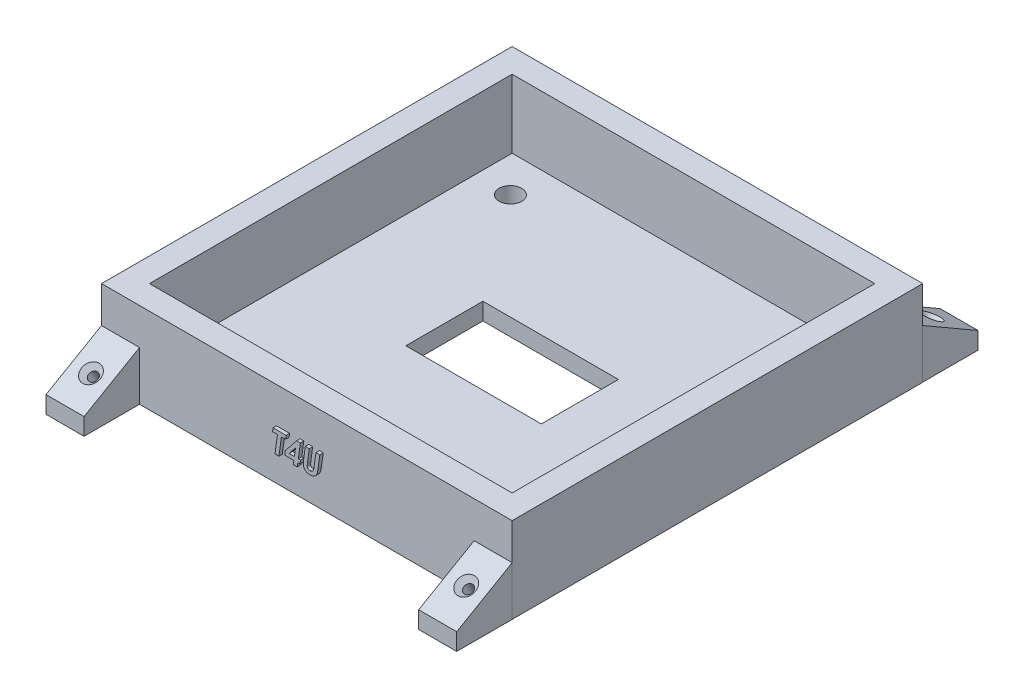
SolidWorks part; units mm, degrees
ref_plane "Front" through (0, 0, 0) normal (0, 0, 1) x (1, 0, 0)
ref_plane "Top" through (0, 0, 0) normal (0, 1, 0) x (1, 0, 0)
ref_plane "Right" through (0, 0, 0) normal (1, 0, 0) x (0, 0, -1)
sketch "Sketch1" plane through (0, 0, 0) normal (0, 1, 0) x (1, 0, 0)
  line L0 (-47.9687, 57.8349) -> (58.0313, 57.8349)
  line L2 (-54.9687, 64.8349) -> (-54.9687, -55.1651)
  line L4 (65.0313, 64.8349) -> (65.0313, -55.1651)
  line L5 (-54.9687, 64.8349) -> (65.0313, -55.1651) construction
  line L6 (-54.9687, -55.1651) -> (65.0313, 64.8349) construction
  line L7 (58.0313, 57.8349) -> (58.0313, -48.1651)
  line L8 (-47.9687, -48.1651) -> (58.0313, -48.1651)
  line L9 (-47.9687, 57.8349) -> (-47.9687, -48.1651)
  line L10 (5.0313, 122.0539) -> (5.0313, -165.2427) construction
  line L16 (-43.869, 64.8349) -> (-43.869, 81.0517)
  line L17 (-54.9687, -72.3819) -> (-54.9687, -55.1651) construction
  line L18 (-111.8398, 4.8349) -> (163.782, 4.8349) construction
  line L19 (-54.9687, -55.1651) -> (-42.869, -72.3819) construction
  line L20 (65.0313, -52.0306) -> (56.1043, -48.1651) construction
  line L24 (53.9479, 81.0517) -> (65.0313, 64.8349) construction
  line L25 (53.9316, 64.8349) -> (64.9733, 81.0517) construction
  line L29 (65.0313, -55.1651) -> (53.1585, -72.537) construction
  line L30 (65.0313, -72.3819) -> (65.0313, -55.1651) construction
  line L34 (53.9316, 64.8349) -> (53.9316, 81.0517)
  line L35 (-14.7657, 16.0987) -> (24.8283, 16.0987)
  line L36 (-14.7657, 16.0987) -> (-14.7657, -6.4289)
  line L37 (-14.7657, -6.4289) -> (24.8283, -6.4289)
  line L38 (24.8283, 16.0987) -> (24.8283, -6.4289)
  line L39 (-14.7657, 16.0987) -> (24.8283, -6.4289) construction
  line L40 (-14.7657, -6.4289) -> (24.8283, 16.0987) construction
  line L41 (64.9733, 81.0517) -> (53.9316, 81.0517)
  line L42 (64.9733, 64.8349) -> (64.9733, 81.0517)
  line L47 (-54.99, -55.1651) -> (-54.99, -71.3819)
  line L48 (-54.99, -71.3819) -> (-43.869, -71.3819)
  line L49 (-43.869, -55.1651) -> (-43.869, -71.3819)
  line L50 (53.9316, -55.1651) -> (53.9316, -71.3819)
  line L51 (65.0476, -71.3819) -> (53.9316, -71.3819)
  line L52 (65.0476, -55.1651) -> (65.0476, -71.3819)
  line L53 (-54.9107, 81.0517) -> (-43.869, 81.0517)
  line L56 (-54.9107, 64.8349) -> (-54.9107, 81.0517)
  line L57 (53.9316, 64.8349) -> (64.9733, 64.8349)
  line L58 (59.4524, 81.0517) -> (59.4524, 64.8349) construction
  line L59 (-54.9687, 64.8349) -> (65.0313, 64.8349) construction
  line L60 (-54.9687, 64.8349) -> (65.0313, 64.8349)
  line L61 (-54.9687, -55.1651) -> (65.0313, -55.1651)
  line L63 (-54.9687, -55.1651) -> (65.0313, -55.1651) construction
  line L64 (53.9316, 72.9433) -> (64.9733, 72.9433) construction
  line L65 (-54.99, -55.1651) -> (-43.869, -55.1651)
  line L66 (-43.869, 64.8349) -> (-54.9107, 64.8349)
  line L69 (53.9316, -55.1651) -> (65.0476, -55.1651)
  line L70 (53.9316, -63.2735) -> (65.0476, -63.2735) construction
  line L71 (59.4896, -71.3819) -> (59.4896, -55.1651) construction
  line L72 (-54.99, -63.2735) -> (-43.869, -63.2735) construction
  line L73 (-49.4295, -71.3819) -> (-49.4295, -55.1651) construction
  line L74 (-54.9107, 72.9433) -> (-43.869, 72.9433) construction
  line L75 (-49.3899, 81.0517) -> (-49.3899, 64.8349) construction
  line L76 (-43.869, 81.0517) -> (-54.9107, 64.8349) construction
  line L77 (-54.9107, 81.0517) -> (-43.869, 64.8349) construction
  point P0 (5.0313, 4.8349)
  point P41 (5.0313, 4.8349)
  dimension "D2" = 7
extrude "Boss-Extrude1" add sketch "Sketch1" along normal blind 5 contours L0 L9 L8 L7 L35 L38 L37 L36 region at (5.0313, 0, -56.3358)
extrude "Boss-Extrude2" add sketch "Sketch1<4>" along normal blind 25 contours L4 L2 L9 L0 L7 L8 region at (-54.9397, 0, -63.1378)
sketch "Sketch1<4>" plane through (0, 0, 0) normal (0, 1, 0) x (1, 0, 0) same geometry as "Sketch1"
extrude "Boss-Extrude4" add sketch "Sketch1<6>" along normal blind 5
sketch "Sketch1<6>" plane through (0, 0, 0) normal (0, 1, 0) x (1, 0, 0) same geometry as "Sketch1"
extrude "Boss-Extrude5" add sketch "Sketch1<8>" along normal blind 5 contours L42 L41 L34 region at (59.4524, 0, -72.9433)
sketch "Sketch1<8>" plane through (0, 0, 0) normal (0, 1, 0) x (1, 0, 0) same geometry as "Sketch1"
extrude "Boss-Extrude7" add sketch "Sketch1<10>" along normal blind 5 contours L69 L50 L51 L52 | L65 L47 L48 L49 region at (-49.4295, 0, 63.2735) region at (59.4896, 0, 63.2735)
sketch "Sketch1<10>" plane through (0, 0, 0) normal (0, 1, 0) x (1, 0, 0) same geometry as "Sketch1"
draft "Draft1" type of draft neutral plane draft angle 1 faces to draft 1 face at (60.598, 5, 61.6518) neutral plane through (0, 5, 71.3819) neutral plane normal (0, 0, 1) parameters "D1"=1
draft "Draft2" type of draft neutral plane draft angle 45 faces to draft 1 face at (60.598, 5.1698, 61.6518) neutral plane through (0, 5, 71.3819) neutral plane normal (0, 0, 1) parameters "D1"=45
draft "Draft3" type of draft neutral plane draft angle 30 faces to draft 1 face at (60.598, 14.7301, 61.6518) neutral plane through (0, 5, 71.3819) neutral plane normal (0, 0, 1) parameters "D1"=30
draft "Draft4" type of draft neutral plane draft angle 30 faces to draft 1 face at (-50.5374, 5, 61.6518) neutral plane through (0, 5, 71.3819) neutral plane normal (0, 0, 1) parameters "D1"=30
draft "Draft6" type of draft neutral plane draft angle 30 faces to draft 1 face at (-49.3899, 5, -72.9433) neutral plane through (0, 5, -81.0517) neutral plane normal (0, 0, -1) parameters "D1"=30
draft "Draft7" type of draft neutral plane draft angle 30 faces to draft 1 face at (59.4524, 5, -72.9433) neutral plane through (0, 5, -81.0517) neutral plane normal (0, 0, -1) parameters "D1"=30
hole_wizard "CSK for M2.5 Oval Head Machine Screw1" positions "3DSketch5" profile "Sketch11" countersink size "M2.5" standard "ANSI Metric" end condition through all
sketch3d "3DSketch5"
  point P0 (59.565, 9.7682, 63.1231)
  point P2 (-49.4297, 9.3781, 63.7988)
  point P5 (58.9935, 9.3349, -73.5435)
  point P7 (-49.4517, 9.6339, -73.0256)
  point P10 (0, 0, 0)
sketch "Sketch11" plane through (59.565, 9.7682, 63.1231) normal (1, 0, 0) x (0, -0.5, 0.866)
  line L0 (0, 0) -> (0, 80.5469)
  line L1 (0, 80.5469) -> (1.35, 80.5469)
  line L2 (1.35, 80.5469) -> (1.35, 1.4)
  line L3 (1.35, 1.4) -> (2.75, 0)
  line L5 (2.75, 0) -> (0, 0)
  line L6 (-1.35, 1.4) -> (-2.75, 0) construction
  line L11 (0, -6.35) -> (0, 107.95) construction
  dimension "Thru Hole Dia." = 2.7
  dimension "Thru Hole Depth" = 80.5469
  dimension "Near C'Sink Dia." = 5.5
  dimension "Near C'Sink Angle" = 90
sketch "Sketch12" plane through (0, 0, 55.1651) normal (0, 0, 1) x (1, 0, 0)
  text T0 "<b><i>T4U</i></b>"
  point P1 (-20.1754, 3.0276)
extrude "Boss-Extrude9" add sketch "Sketch12" along normal blind 1
sketch "Sketch14" plane through (0, 0, 0) normal (0, -1, 0) x (-1, 0, 0)
  circle A0 centre (37.6942, -37.9802) radius 3.2963
  circle A1 centre (-47.3112, -37.942) radius 3.2963
  circle A2 centre (-47.3112, 47.058) radius 3.2963
  circle A3 centre (37.6888, 47.058) radius 3.2963
extrude "Cut-Extrude1" cut sketch "Sketch14" against normal blind 10
